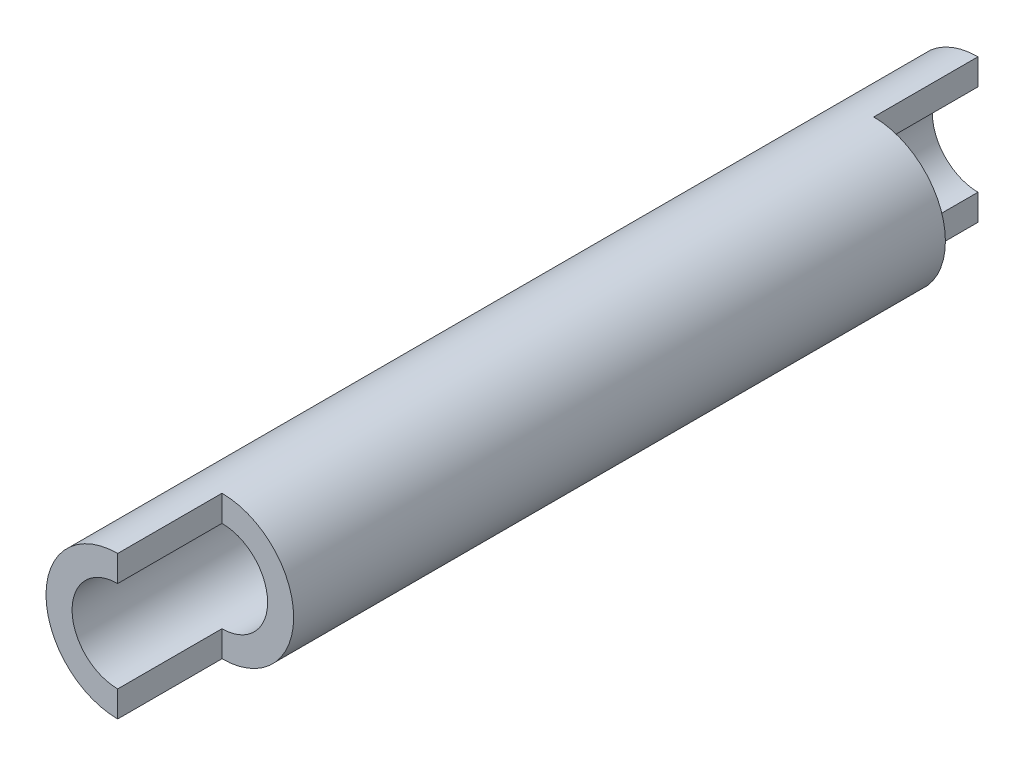
SolidWorks part; units mm, degrees
ref_plane "Płaszczyzna przednia" through (0, 0, 0) normal (0, 0, 1) x (1, 0, 0)
ref_plane "Płaszczyzna górna" through (0, 0, 0) normal (0, 1, 0) x (1, 0, 0)
ref_plane "Płaszczyzna prawa" through (0, 0, 0) normal (1, 0, 0) x (0, 0, -1)
sketch "Sketch1" plane through (0, 0, 0) normal (0, 0, 1) x (1, 0, 0)
  line L0 (-5.5, 0) -> (0, 0) construction
  line L1 (0, 0) -> (0, -5.5) construction
  circle A1 centre (0, 0) radius 3.5
  circle A2 centre (0, 0) radius 5.5
  dimension "D1" = 7
  dimension "D2" = 11
extrude "Boss-Extrude1 dlugosc calkowita" add sketch "Sketch1" along normal blind 50
sketch "Sketch2" plane through (0, 0, 0) normal (0, 0, -1) x (-1, 0, 0)
  line L0 (0, 5.5) -> (0, 3.5)
  line L1 (0, -3.5) -> (0, -5.5)
  arc A0 (0, -5.5) -> (0, 5.5) centre (0, 0) ccw
  arc A1 (0, -3.5) -> (0, 3.5) centre (0, 0) ccw
  circle A2 centre (0, 0) radius 5.5 construction
  dimension "D1" = 5.5
  dimension "D2" = 3.5
extrude "Boss-Extrude2 przedluzenie do montazu" add sketch "Sketch2" along normal blind 8 and the other way offset from surface (58 mm away) 8 other way up to face at (5.5, 0, 50)
equation "\"D1@Boss-Extrude1 dlugosc calkowita\" = \"dlugosc S2\""
equation "\"dlugosc S3\"= 150"
equation "\"dlugosc S4\"= 150"
equation "\"dlugosc S1\"= 1"
equation "\"dlugosc S2\"= 50"
